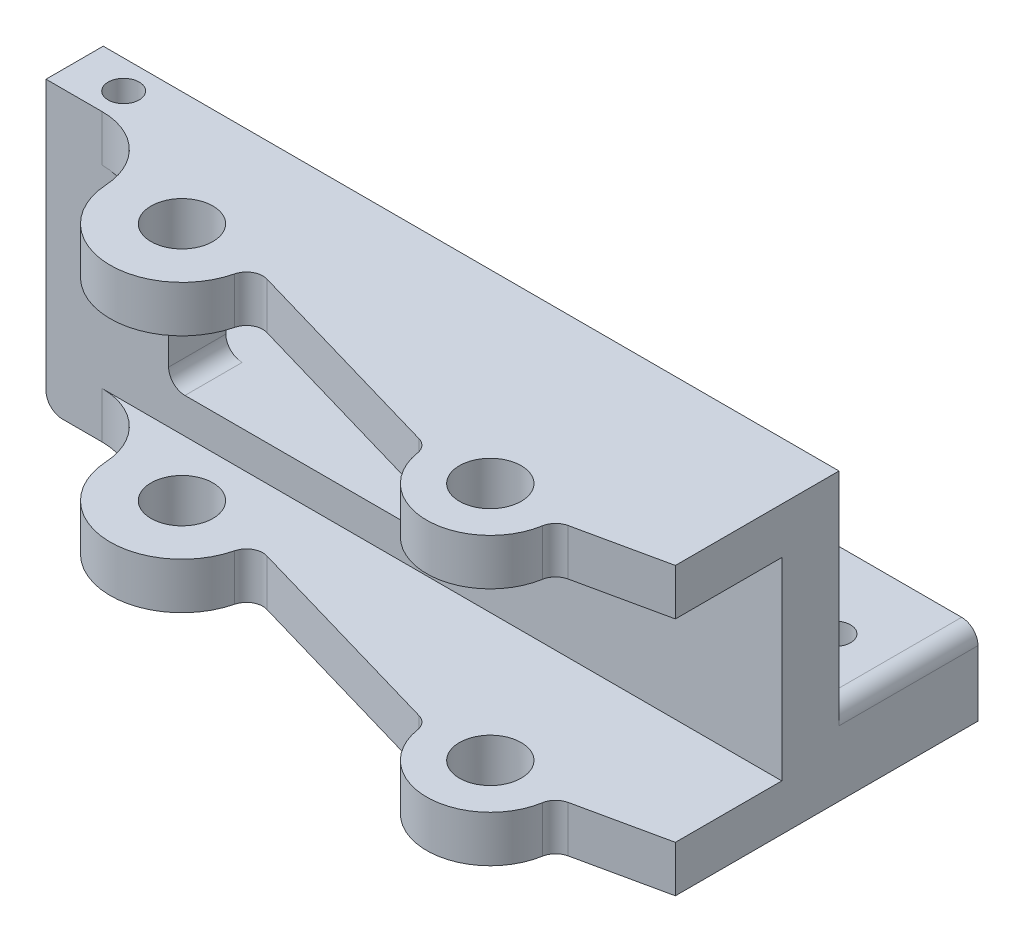
SolidWorks part; units mm, degrees
ref_plane "Front Plane" through (0, 0, 0) normal (0, 0, 1) x (1, 0, 0)
ref_plane "Top Plane" through (0, 0, 0) normal (0, 1, 0) x (1, 0, 0)
ref_plane "Right Plane" through (0, 0, 0) normal (1, 0, 0) x (0, 0, -1)
sketch "Sketch1" plane through (0, 0, 0) normal (0, 0, 1) x (1, 0, 0)
  line L1 (57.15, -22.225) -> (-57.15, -22.225)
  line L2 (57.15, -22.225) -> (57.15, 22.225)
  line L3 (57.15, 22.225) -> (-57.15, 22.225)
  line L4 (-57.15, -22.225) -> (-57.15, 22.225)
  line L5 (57.15, -22.225) -> (-57.15, 22.225) construction
  line L6 (57.15, 22.225) -> (-57.15, -22.225) construction
  point P0 (0, 0)
  dimension "D1" = 44.45
  dimension "D2" = 114.3
extrude "Boss-Extrude1" add sketch "Sketch1" along normal blind 62.23
sketch "Sketch2" plane through (0, 0, 62.23) normal (0, 0, 1) x (1, 0, 0)
  line L0 (-57.15, 22.225) -> (-57.15, -22.225) construction
  line L1 (57.15, -15.025) -> (-57.15, -15.025)
  line L2 (57.15, -15.025) -> (57.15, 15.025)
  line L3 (57.15, 15.025) -> (-57.15, 15.025)
  line L4 (-57.15, -15.025) -> (-57.15, 15.025)
  line L5 (57.15, -15.025) -> (-57.15, 15.025) construction
  line L6 (57.15, 15.025) -> (-57.15, -15.025) construction
  line L7 (57.15, 22.225) -> (-57.15, 22.225) construction
  point P0 (0, 0)
  dimension "D1" = 7.2
extrude "Cut-Extrude2" cut sketch "Sketch2" against normal blind 31.75
sketch "Sketch3" plane through (0, 0, 0) normal (0, 0, -1) x (-1, 0, 0)
  line L0 (-57.15, -22.225) -> (-57.15, 22.225) construction
  line L1 (57.15, 22.225) -> (-57.15, 22.225)
  line L2 (57.15, 22.225) -> (57.15, -9.525)
  line L3 (57.15, -9.525) -> (-57.15, -9.525)
  line L4 (-57.15, 22.225) -> (-57.15, -9.525)
  line L5 (57.15, -22.225) -> (-57.15, -22.225) construction
  dimension "D1" = 12.7
extrude "Cut-Extrude3" cut sketch "Sketch3" against normal blind 21.59
sketch "Sketch5" plane through (0, -22.225, 0) normal (0, -1, 0) x (1, 0, 0)
  line L0 (-3.81, 12.06) -> (46.99, 12.06) construction
  line L1 (57.15, 21.59) -> (-57.15, 21.59) construction
  line L2 (57.15, 62.23) -> (57.15, 0) construction
  circle A0 centre (-3.81, 12.06) radius 2.415
  circle A1 centre (46.99, 12.06) radius 2.415
  dimension "D3" = 4.83
  dimension "D4" = 10.16
  dimension "D1" = 9.53
  dimension "D2" = 50.8
extrude "Cut-Extrude4" cut sketch "Sketch5" against normal blind 25.4
sketch "Sketch7" plane through (0, -22.225, 0) normal (0, -1, 0) x (1, 0, 0)
  line L0 (57.15, 62.23) -> (57.15, 0) construction
  line L1 (-57.15, 0) -> (57.15, 0) construction
  circle A0 centre (31.75, 50.36) radius 4.8
  circle A1 centre (-27.14, 39.37) radius 4.8
  dimension "D1" = 9.6
  dimension "D2" = 25.4
  dimension "D3" = 39.37
  dimension "D4" = 9.6
  dimension "D5" = 58.89
  dimension "D6" = 10.99
extrude "Cut-Extrude6" cut sketch "Sketch7" against normal up to surface (44.45 mm away) up to face at (0, 22.225, 41.91)
sketch "Sketch9" plane through (0, 0, 30.48) normal (0, 0, 1) x (1, 0, 0)
  line L5 (57.15, 15.025) -> (-57.15, 15.025) construction
  line L6 (-38.1, 15.025) -> (6.35, 15.025)
  line L7 (-38.1, 15.025) -> (-38.1, -15.025)
  line L8 (-38.1, -15.025) -> (6.35, -15.025)
  line L9 (6.35, 15.025) -> (6.35, -15.025)
  line L10 (-57.15, -15.025) -> (57.15, -15.025) construction
  line L11 (-57.15, 15.025) -> (-57.15, -15.025) construction
  line L12 (57.15, -15.025) -> (57.15, 15.025) construction
  dimension "D1" = 50.8
  dimension "25in" = 19.05
extrude "Cut-Extrude7" cut sketch "Sketch9" against normal through all both and the other way through all
sketch "Sketch16" plane through (0, -22.225, 0) normal (0, -1, 0) x (1, 0, 0)
  line L1 (-38.1, 30.48) -> (-57.15, 30.48) construction
  line L8 (-57.15, 62.23) -> (57.15, 62.23)
  line L9 (57.15, 62.23) -> (57.15, 47.0103)
  line L10 (57.15, 62.23) -> (57.15, 0) construction
  line L11 (-15.99, 39.37) -> (21.87, 50.36)
  line L12 (41.63, 50.36) -> (57.15, 47.0103)
  line L13 (-48.4121, 30.48) -> (-57.15, 30.48)
  line L15 (-57.15, 30.48) -> (-57.15, 62.23)
  arc A2 (41.63, 50.36) -> (21.87, 50.36) centre (31.75, 50.36) ccw
  arc A3 (-15.99, 39.37) -> (-38.2702, 40.0345) centre (-27.14, 39.37) ccw
  circle A4 centre (-27.14, 39.37) radius 4.8 construction
  circle A5 centre (31.75, 50.36) radius 4.8 construction
  arc A6 (-48.4121, 30.48) -> (-38.2702, 40.0345) centre (-48.4121, 40.64) ccw
  dimension "D1" = 6.35
  dimension "D2" = 5.08
  dimension "D3" = 10.16
extrude "Cut-Extrude8" cut sketch "Sketch16" against normal through all
fillet "Fillet1" radius 2.54 6 edges at (21.87, 18.625, 50.36) (41.63, -18.625, 50.36) (41.63, 18.625, 50.36) (-15.99, 18.625, 39.37) (-15.99, -18.625, 39.37) (21.87, -18.625, 50.36)
sketch "Sketch14" plane through (6.35, 0, 0) normal (-1, 0, 0) x (0, 0, 1)
  line L0 (0, -15.025) -> (30.48, -15.025) construction
  line L1 (21.59, -9.525) -> (0, -9.525)
  line L2 (21.59, -9.525) -> (21.59, -15.025)
  line L3 (21.59, -15.025) -> (0, -15.025)
  line L4 (0, -9.525) -> (0, -15.025)
extrude "Boss-Extrude2" add sketch "Sketch14" along normal up to next
sketch "Sketch17" plane through (0, 0, 21.59) normal (0, 0, 1) x (1, 0, 0)
  line L1 (6.35, -15.025) -> (-38.1, -15.025)
  line L2 (6.35, -15.025) -> (6.35, -9.525)
  line L3 (6.35, -9.525) -> (-38.1, -9.525)
  line L4 (-38.1, -15.025) -> (-38.1, -9.525)
extrude "Boss-Extrude3" add sketch "Sketch17" along normal up to surface (8.89 mm away) up to face at (31.75, 0, 30.48)
sketch "Sketch18" plane through (-57.15, 0, 0) normal (-1, 0, 0) x (0, 0, 1)
  line L0 (30.48, 22.225) -> (30.48, -22.225) construction
  line L1 (21.59, 22.225) -> (30.48, 22.225)
  line L2 (21.59, 22.225) -> (21.59, -22.225)
  line L3 (21.59, -22.225) -> (30.48, -22.225)
  line L4 (30.48, 22.225) -> (30.48, -22.225)
  line L5 (21.59, 22.225) -> (30.48, -22.225) construction
  line L6 (21.59, -22.225) -> (30.48, 22.225) construction
  line L7 (30.48, -22.225) -> (0, -22.225) construction
  line L8 (21.59, -9.525) -> (21.59, 22.225) construction
  line L9 (30.48, 22.225) -> (21.59, 22.225) construction
  point P0 (26.035, 0)
sketch "Sketch20" plane through (0, 0, 21.59) normal (0, 0, -1) x (-1, 0, 0)
  line L0 (38.1, 15.025) -> (38.1, -9.525) construction
  line L1 (38.1, 38.1) -> (88.9, 38.1)
  line L2 (38.1, 38.1) -> (38.1, -38.1)
  line L3 (38.1, -38.1) -> (88.9, -38.1)
  line L4 (88.9, 38.1) -> (88.9, -38.1)
  line L5 (38.1, 38.1) -> (88.9, -38.1) construction
  line L6 (38.1, -38.1) -> (88.9, 38.1) construction
  point P0 (63.5, 0)
  point P9 (88.9, 0)
  dimension "D1" = 76.2
  dimension "D2" = 50.8
sketch "Sketch21" plane through (0, 0, 30.48) normal (0, 0, 1) x (1, 0, 0)
  line L0 (-54.61, -20.32) -> (-54.61, -19.685)
  line L13 (-54.61, 19.685) -> (-54.61, -19.685)
  line L14 (-54.61, 19.685) -> (-54.61, -19.685)
  line L16 (-50.9521, -12.485) -> (-40.64, -12.485)
  line L17 (-40.64, -12.485) -> (-40.64, -12.065)
  line L34 (-54.61, -19.685) -> (-50.9521, -19.685)
  line L35 (-50.9521, -19.685) -> (-50.9521, -12.485)
  line L36 (-50.9521, -12.485) -> (54.61, -12.485)
  line L37 (54.61, -12.485) -> (54.61, 12.485)
  line L38 (54.61, 12.485) -> (8.89, 12.485)
  line L39 (8.89, 12.485) -> (8.89, -12.065)
  line L40 (8.89, -12.065) -> (-40.64, -12.065)
  line L41 (-40.64, -12.065) -> (-40.64, 12.485)
  line L42 (-40.64, 12.485) -> (-50.9521, 12.485)
  line L43 (-50.9521, 12.485) -> (-50.9521, 19.685)
  line L44 (-50.9521, 19.685) -> (-54.61, 19.685)
  line L50 (-54.61, -19.685) -> (-50.9521, -19.685)
  line L51 (-50.9521, -19.685) -> (-50.9521, -12.485)
  line L57 (-40.64, -12.065) -> (-40.64, 12.485)
  line L58 (-40.64, 12.485) -> (-50.9521, 12.485)
  line L59 (-50.9521, 12.485) -> (-50.9521, 19.685)
  line L60 (-50.9521, 19.685) -> (-54.61, 19.685)
  dimension "D1" = 2.54
fillet "Fillet6" radius 2.54 7 edges at (6.35, -9.525, 26.035) (6.35, 15.025, 26.035) (-38.1, 15.025, 26.035) (-38.1, -9.525, 26.035) (57.15, -9.525, 10.795) (-57.15, -9.525, 10.795) (-57.15, -22.225, 15.24)
sketch "Sketch23" plane through (0, 22.225, 0) normal (0, 1, 0) x (1, 0, 0)
  line L0 (-57.15, -30.48) -> (-57.15, -21.59) construction
  line L1 (-57.15, -30.48) -> (-48.4121, -30.48) construction
  circle A0 centre (-49.53, -26.035) radius 2.413
  dimension "D1" = 4.826
  dimension "D2" = 7.62
  dimension "D3" = 4.445
extrude "Cut-Extrude9" cut sketch "Sketch23" against normal through all
